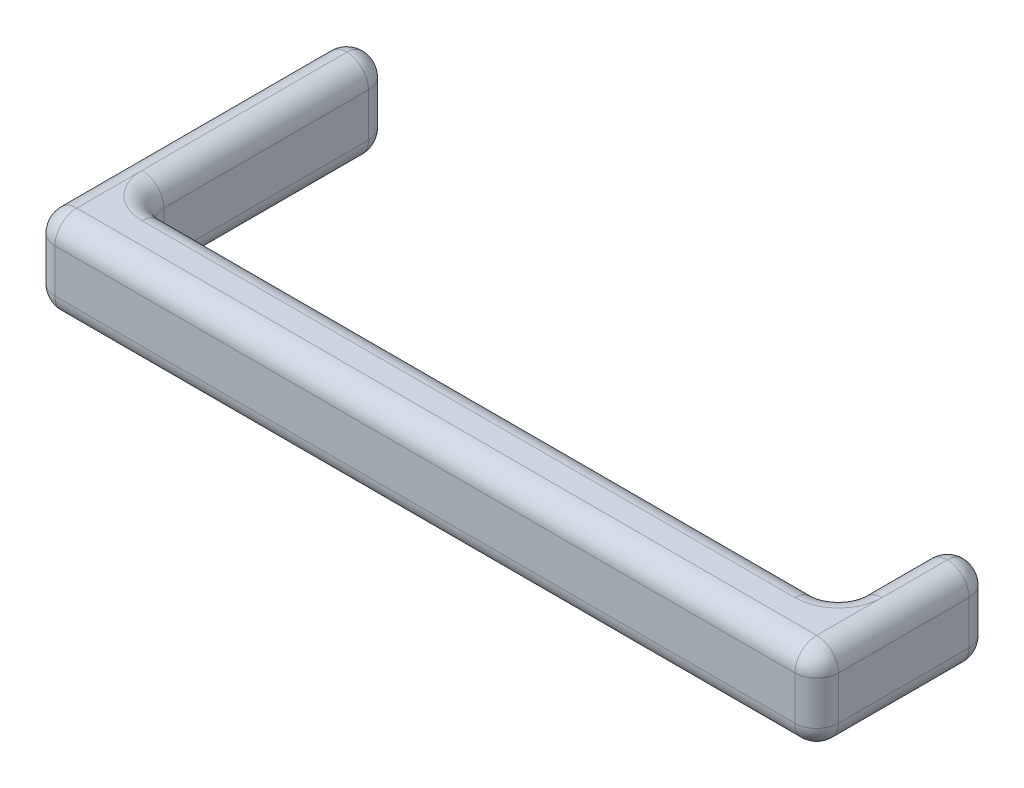
SolidWorks part; units mm, degrees
ref_plane "Front Plane" through (0, 0, 0) normal (0, 0, 1) x (1, 0, 0)
ref_plane "Top Plane" through (0, 0, 0) normal (0, 1, 0) x (1, 0, 0)
ref_plane "Right Plane" through (0, 0, 0) normal (1, 0, 0) x (0, 0, -1)
sketch "Sketch1" plane through (0, 0, 0) normal (0, 0, 1) x (1, 0, 0)
  line L1 (0, 0) -> (-812.8, 0)
  line L2 (0, 0) -> (0, 101.6)
  line L3 (0, 101.6) -> (-812.8, 101.6)
  line L4 (-812.8, 0) -> (-812.8, 101.6)
  dimension "D1" = 812.8
  dimension "D2" = 101.6
extrude "Boss-Extrude1" add sketch "Sketch1" along normal blind 76.2
sketch "Sketch2" plane through (0, 0, 76.2) normal (0, 0, 1) x (1, 0, 0)
  line L1 (-812.8, 101.6) -> (-863.6, 101.6)
  line L2 (-812.8, 101.6) -> (-812.8, 0)
  line L3 (-812.8, 0) -> (-863.6, 0)
  line L4 (-863.6, 101.6) -> (-863.6, 0)
  line L5 (0, 101.6) -> (50.8, 101.6)
  line L6 (0, 101.6) -> (0, 0)
  line L7 (0, 0) -> (50.8, 0)
  line L8 (50.8, 101.6) -> (50.8, 0)
  dimension "D1" = 50.8
  dimension "D2" = 50.8
extrude "Boss-Extrude2" add sketch "Sketch2" against normal blind 203.2 contours L4 L3 L2 L1 | L6 L5 L8 L7
sketch "Sketch6" plane through (-863.6, 0, 0) normal (-1, 0, 0) x (0, 0, 1)
  line L1 (76.2, 0) -> (-289.687, 0)
  line L2 (76.2, 0) -> (76.2, 101.6)
  line L3 (76.2, 101.6) -> (-289.687, 101.6)
  line L4 (-289.687, 0) -> (-289.687, 101.6)
  dimension "D1" = 365.887
extrude "Boss-Extrude5" add sketch "Sketch6" against normal up to surface (50.8 mm away) up to face at (-812.8, 50.8, -63.5)
fillet "Fillet4" radius 25.4 24 edges at (-863.6, 50.8, 76.2) (-863.6, 0, -106.7435) (-406.4, 0, 76.2) (0, 0, -63.5) (-812.8, 0, -144.8435) (-812.8, 101.6, -144.8435) (0, 101.6, -63.5) (-406.4, 101.6, 76.2) (-863.6, 101.6, -106.7435) (-838.2, 101.6, -289.687) (-863.6, 50.8, -289.687) (-838.2, 0, -289.687) (-812.8, 50.8, -289.687) (25.4, 101.6, -127) (0, 50.8, -127) (25.4, 0, -127) (-406.4, 101.6, 0) (-812.8, 50.8, 0) (-406.4, 0, 0) (0, 50.8, 0) (50.8, 101.6, -25.4) (50.8, 50.8, -127) (50.8, 0, -25.4) (50.8, 50.8, 76.2)
